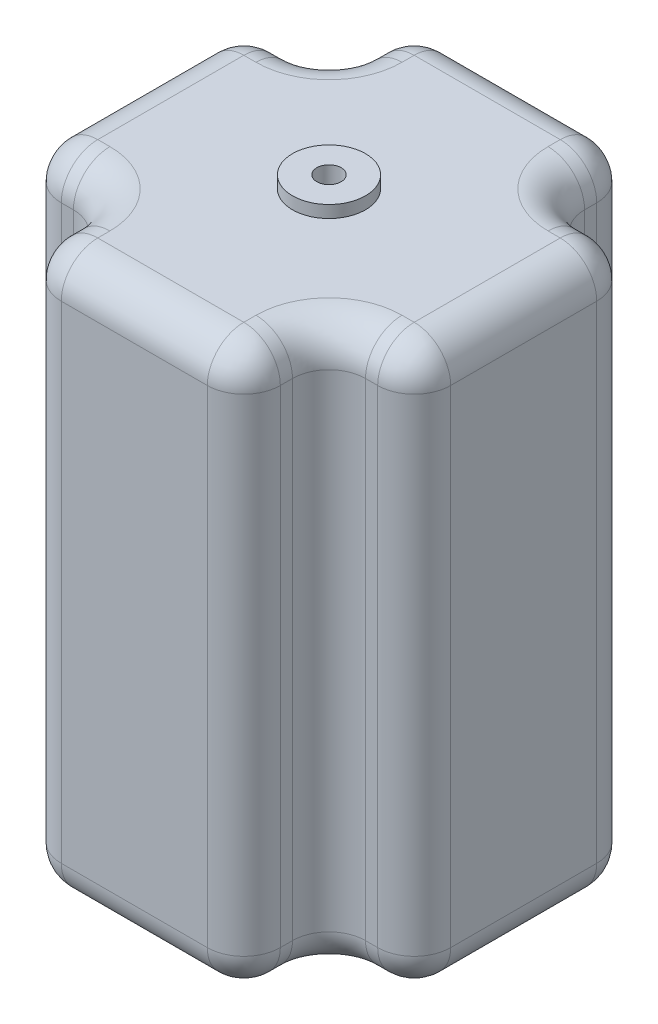
SolidWorks part; units mm, degrees
ref_plane "Front Plane" through (0, 0, 0) normal (0, 0, 1) x (1, 0, 0)
ref_plane "Top Plane" through (0, 0, 0) normal (0, 1, 0) x (1, 0, 0)
ref_plane "Right Plane" through (0, 0, 0) normal (1, 0, 0) x (0, 0, -1)
sketch "Sketch1" plane through (0, 0, 0) normal (0, 1, 0) x (1, 0, 0)
  line L0 (-9, 9) -> (-9, 16)
  line L1 (-9, -16) -> (9, -16)
  line L2 (-9, -16) -> (-9, -9)
  line L3 (-9, 16) -> (9, 16)
  line L4 (9, -16) -> (9, -9)
  line L5 (-9, -16) -> (9, 16) construction
  line L6 (-9, 16) -> (9, -16) construction
  line L7 (-16, -9) -> (-9, -9)
  line L8 (-16, -9) -> (-16, 9)
  line L9 (-16, 9) -> (-9, 9)
  line L10 (16, -9) -> (16, 9)
  line L11 (-16, -9) -> (16, 9) construction
  line L12 (-16, 9) -> (16, -9) construction
  line L13 (9, 9) -> (16, 9)
  line L14 (9, 9) -> (9, 16)
  line L15 (9, -9) -> (16, -9)
  point P0 (0, 0)
  point P6 (0, 0)
  dimension "D1" = 18
  dimension "D2" = 7
extrude "Boss-Extrude1" add sketch "Sketch1" along normal blind 46
fillet "Fillet1" radius 3 36 edges at (9, 23, 16) (-9, 23, 16) (-16, 0, 0) (-9, 0, 12.5) (0, 0, 16) (9, 0, 12.5) (-9, 0, -12.5) (-9, 23, -9) (-16, 23, -9) (-12.5, 0, -9) (-9, 23, -16) (0, 0, -16) (9, 23, -16) (9, 0, -12.5) (9, 23, -9) (12.5, 0, -9) (12.5, 46, -9) (9, 46, 12.5) (0, 46, 16) (-9, 46, 12.5) (-16, 46, 0) (-12.5, 46, -9) (-9, 46, -12.5) (0, 46, -16) (9, 46, -12.5) (-16, 23, 9) (-12.5, 46, 9) (-9, 23, 9) (-12.5, 0, 9) (16, 46, 0) (16, 23, -9) (16, 0, 0) (9, 23, 9) (12.5, 46, 9) (16, 23, 9) (12.5, 0, 9)
sketch "Sketch2" plane through (0, 46, 0) normal (0, 1, 0) x (1, 0, 0)
  circle A0 centre (0, 0) radius 3
extrude "Boss-Extrude2" add sketch "Sketch2" along normal blind 1
shell "Shell1" thickness 2 removed face at (0, 47, 3)
